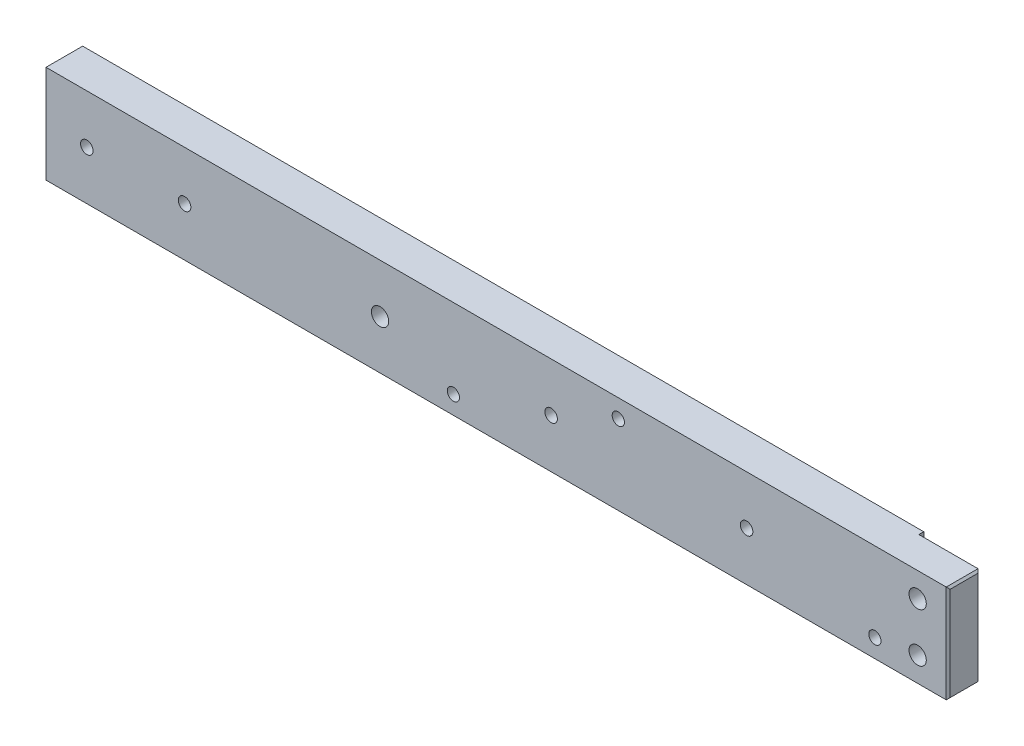
SolidWorks part; units mm, degrees
material "6061-T6 (SS)"
ref_plane "Front Plane" through (0, 0, 0) normal (0, 0, 1) x (1, 0, 0)
ref_plane "Top Plane" through (0, 0, 0) normal (0, 1, 0) x (1, 0, 0)
ref_plane "Right Plane" through (0, 0, 0) normal (1, 0, 0) x (0, 0, -1)
sketch "Sketch1" plane through (0, 0, 0) normal (0, 0, 1) x (1, 0, 0)
  line L1 (0, 0) -> (-234.95, 0)
  line L2 (0, 0) -> (0, 25.4)
  line L3 (0, 25.4) -> (-234.95, 25.4)
  line L4 (-234.95, 0) -> (-234.95, 25.4)
  dimension "D1" = 25.4
  dimension "D2" = 234.95
extrude "Boss-Extrude1" add sketch "Sketch1" along normal blind 9.525
sketch "Sketch2" plane through (0, 0, 9.525) normal (0, 0, 1) x (1, 0, 0)
  line L0 (-7.9375, 6.35) -> (-7.9375, 19.05)
  line L1 (-7.9375, 19.05) -> (-7.9375, 25.4)
  line L2 (0, 25.4) -> (-234.95, 25.4) construction
  line L3 (-7.9375, 6.35) -> (-7.9375, 0)
  line L4 (-234.95, 0) -> (0, 0) construction
  line L5 (0, 0) -> (0, 25.4) construction
  dimension "D1" = 7.9375
  dimension "D2" = 12.7
hole_wizard "#8 Clearance Hole1" positions "Sketch3" profile "Sketch4" hole size "#8" standard "ANSI Inch"
sketch "Sketch3" plane through (0, 0, 9.525) normal (0, 0, 1) x (1, 0, 0)
  point P0 (-7.9375, 6.35)
  point P3 (-7.9375, 19.05)
sketch "Sketch4" plane through (-7.9375, 6.35, 9.525) normal (1, 0, 0) x (0, -1, 0)
  line L0 (0, 0) -> (0, 26.7507)
  line L1 (0, 26.7507) -> (2.2479, 25.4)
  line L2 (2.2479, 25.4) -> (2.2479, 0)
  line L5 (2.2479, 0) -> (0, 0)
  line L10 (0, 26.7507) -> (-2.2479, 25.4) construction
  line L11 (0, -6.35) -> (0, 107.95) construction
  dimension "Hole Dia." = 4.4958
  dimension "Hole Depth" = 25.4
  dimension "Drill Angle" = 118
hole_wizard "#8 Clearance Hole2" positions "Sketch8" profile "Sketch9" hole size "#8" standard "ANSI Inch"
sketch "Sketch8" plane through (0, 0, 9.525) normal (0, 0, 1) x (1, 0, 0)
  line L0 (-211.1375, 12.7) -> (-147.6375, 12.7)
  line L1 (-211.1375, 12.7) -> (-234.95, 12.7)
  line L2 (-234.95, 25.4) -> (-234.95, 0) construction
  point P2 (-147.6375, 12.7)
  dimension "D1" = 63.5
  dimension "D2" = 23.8125
sketch "Sketch9" plane through (-147.6375, 12.7, 9.525) normal (1, 0, 0) x (0, -1, 0)
  line L0 (0, 0) -> (0, 20.4007)
  line L1 (0, 20.4007) -> (2.2479, 19.05)
  line L2 (2.2479, 19.05) -> (2.2479, 0)
  line L5 (2.2479, 0) -> (0, 0)
  line L10 (0, 20.4007) -> (-2.2479, 19.05) construction
  line L11 (0, -6.35) -> (0, 107.95) construction
  dimension "Hole Dia." = 4.4958
  dimension "Hole Depth" = 19.05
  dimension "Drill Angle" = 118
hole_wizard "#4 Clearance Hole3" positions "Sketch10" profile "Sketch12" hole size "#4" standard "ANSI Inch" end condition through all
sketch "Sketch10" plane through (0, 0, 0) normal (0, 0, -1) x (-1, 0, 0)
  circle A0 centre (52.3875, 12.7) radius 1.1303 construction
  circle A1 centre (52.3875, 12.7) radius 1.1303
  circle A2 centre (103.1875, 12.7) radius 1.1303 construction
  circle A3 centre (103.1875, 12.7) radius 1.1303
  point P0 (103.1875, 12.7)
  point P3 (52.3875, 12.7)
sketch "Sketch12" plane through (-103.1875, 12.7, 0) normal (1, 0, 0) x (0, 1, 0)
  line L0 (0, 0) -> (0, 9.525)
  line L1 (0, 9.525) -> (1.6319, 9.525)
  line L2 (1.6319, 9.525) -> (1.6319, 0)
  line L5 (1.6319, 0) -> (0, 0)
  line L11 (0, -6.35) -> (0, 107.95) construction
  dimension "Thru Hole Dia." = 3.2639
  dimension "Thru Hole Depth" = 9.525
hole_wizard "#4 Clearance Hole2" positions "Sketch13" profile "Sketch14" hole size "#4" standard "ANSI Inch" end condition up to next
sketch "Sketch13" plane through (0, 0, 9.525) normal (0, 0, 1) x (1, 0, 0)
  line L0 (-223.8375, 12.7) -> (-198.4375, 12.7)
  line L3 (-147.6375, 12.7) -> (-211.1375, 12.7) construction
  point P0 (-223.8375, 12.7)
  point P2 (-198.4375, 12.7)
  dimension "D1" = 25.4
  dimension "D2" = 63.5
sketch "Sketch14" plane through (-223.8375, 12.7, 9.525) normal (1, 0, 0) x (0, -1, 0)
  line L0 (0, 0) -> (0, 9.525)
  line L1 (0, 9.525) -> (1.6319, 9.525)
  line L2 (1.6319, 9.525) -> (1.6319, 0)
  line L5 (1.6319, 0) -> (0, 0)
  line L11 (0, -6.35) -> (0, 107.95) construction
  dimension "Thru Hole Dia." = 3.2639
  dimension "Thru Hole Depth" = 9.525
hole_wizard "1/8 (0.125) Diameter Hole1" positions "Sketch15" profile "Sketch17" hole size "1/8" standard "ANSI Inch" end condition up to next
sketch "Sketch15" plane through (0, 0, 9.525) normal (0, 0, 1) x (1, 0, 0)
  line L2 (-85.725, 20.6375) -> (-19.05, 4.7625)
  line L6 (-234.95, 0) -> (0, 0) construction
  line L7 (-234.95, 0) -> (0, 0) construction
  line L8 (0, 25.4) -> (-234.95, 25.4) construction
  line L10 (-134.9375, 0) -> (-134.9375, 25.4) construction
  line L11 (0, 0) -> (0, 25.4) construction
  point P0 (-19.05, 4.7625)
  point P2 (-85.725, 20.6375)
  point P22 (-128.5875, 4.7625)
  dimension "D1" = 66.675
  dimension "D2" = 19.05
  dimension "D3" = 4.7625
  dimension "D4" = 4.7625
  dimension "D5" = 6.35
  dimension "D6" = 4.7625
sketch "Sketch17" plane through (-19.05, 4.7625, 9.525) normal (1, 0, 0) x (0, -1, 0)
  line L0 (0, 0) -> (0, 9.525)
  line L1 (0, 9.525) -> (1.5875, 9.525)
  line L2 (1.5875, 9.525) -> (1.5875, 0)
  line L5 (1.5875, 0) -> (0, 0)
  line L11 (0, -6.35) -> (0, 107.95) construction
  dimension "Thru Hole Dia." = 3.175
  dimension "Thru Hole Depth" = 9.525
sketch "Sketch18" plane through (0, 0, 0) normal (0, 0, -1) x (-1, 0, 0)
  line L0 (0, 25.4) -> (234.95, 25.4) construction
  line L1 (0, 0) -> (15.875, 0)
  line L2 (0, 0) -> (0, 25.4)
  line L3 (0, 25.4) -> (15.875, 25.4)
  line L4 (15.875, 0) -> (15.875, 25.4)
  circle A0 centre (7.9375, 6.35) radius 2.2479 construction
  circle A1 centre (7.9375, 6.35) radius 2.2479
  dimension "D1" = 7.9375
extrude "Cut-Extrude1" cut sketch "Sketch18" against normal blind 1.27
chamfer "Chamfer1" distance 0.508 angle 45 8 edges at (-234.95, 25.4, 4.7625) (-234.95, 12.7, 9.525) (-234.95, 0, 4.7625) (-234.95, 12.7, 0) (0, 12.7, 9.525) (0, 25.4, 5.3975) (0, 12.7, 1.27) (0, 0, 5.3975)
